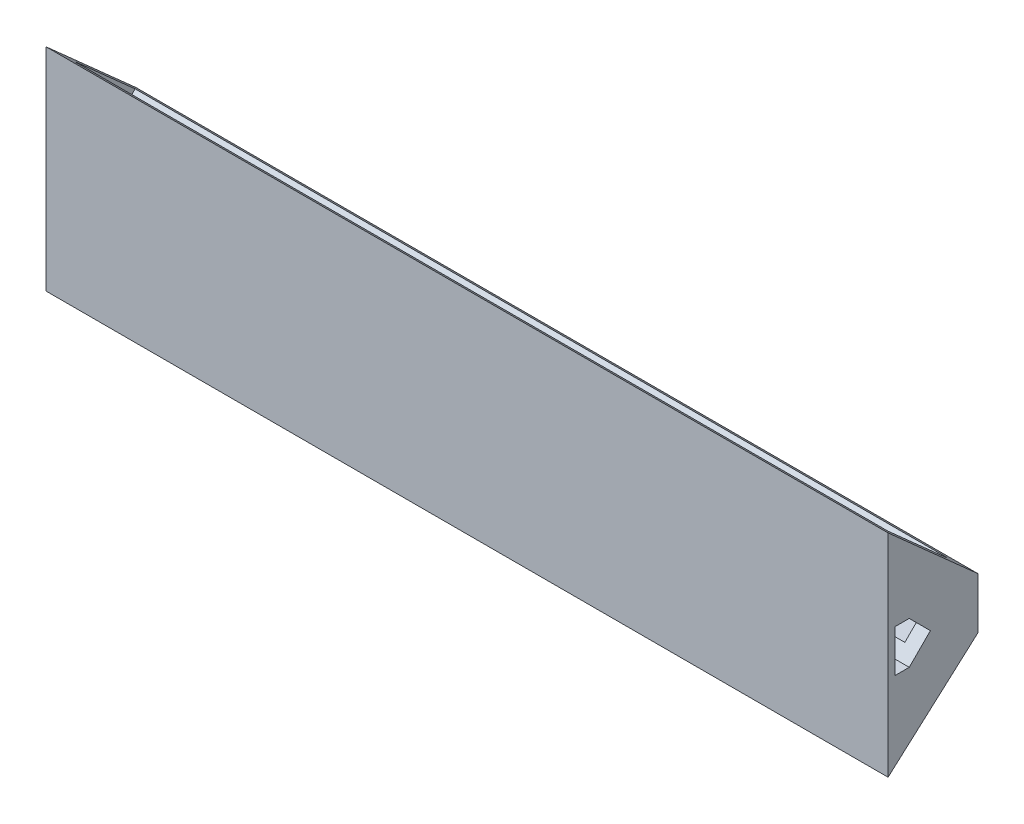
SolidWorks part; units mm, degrees
ref_plane "Front Plane" through (0, 0, 0) normal (0, 0, 1) x (1, 0, 0)
ref_plane "Top Plane" through (0, 0, 0) normal (0, 1, 0) x (1, 0, 0)
ref_plane "Right Plane" through (0, 0, 0) normal (1, 0, 0) x (0, 0, -1)
sketch "Sketch1" plane through (0, 0, 0) normal (0, 0, 1) x (1, 0, 0)
  line L0 (-115.4, 3.25) -> (115.4, -3.25) construction
  line L1 (-115.4, 3.25) -> (115.4, 3.25)
  line L2 (-115.4, 3.25) -> (-115.4, -3.25)
  line L3 (-115.4, -3.25) -> (115.4, -3.25)
  line L4 (115.4, 3.25) -> (115.4, -3.25)
  line L5 (-119.4, 7.25) -> (-119.4, -7.25)
  line L6 (-119.4, -7.25) -> (119.4, -7.25)
  line L7 (119.4, 7.25) -> (119.4, -7.25)
  line L8 (-119.4, 7.25) -> (119.4, 7.25)
  dimension "D1" = 6.5
  dimension "D2" = 230.8
  dimension "D3" = 4
sketch "Sketch4" plane through (0, 0, 0) normal (1, 0, 0) x (0, 0, -1)
  line L0 (-20, 8.7261) -> (-20, -2.0023) construction
  line L1 (0, 7.25) -> (0, -7.25) construction
  line L2 (0, 7.25) -> (-25.5, 30)
  line L3 (-25.5, 30) -> (-25.5, -30)
  line L4 (-25.5, 0) -> (0, 0) construction
  line L5 (-23.5, 6) -> (-23.5, -6)
  line L6 (-23.5, 6) -> (-19.5, 6)
  line L7 (-19.5, 6) -> (-13.5, 0)
  line L8 (-20.5, 4.0321) -> (-20.5, -1.7233) construction
  line L9 (0, -7.25) -> (-25.5, -30)
  line L10 (-19.5, -6) -> (-13.5, 0)
  line L11 (-23.5, -6) -> (-19.5, -6)
  line L12 (0, 7.25) -> (0, -7.25)
  point P22 (-23.5, 0)
  dimension "D1" = 20
  dimension "D2" = 3
  dimension "D3" = 2
  dimension "D4" = 45
  dimension "D5" = 0.5
  dimension "D6" = 6
  dimension "D7" = 4
  dimension "D8" = 30
extrude "Boss-Extrude1" add sketch "Sketch4" along normal up to vertex (119.4 mm away) and the other way up to vertex (119.4 mm away) up to point (119.4, 7.25, 0) other way up to point (-119.4, 7.25, 0)
extrude "Cut-Extrude1" cut sketch "Sketch1" along normal blind 20 contours L1 L4 L3 L2
shell "Shell1" thickness 4 removed face at (0, 18.625, 12.75) removed face at (0, -18.625, 12.75)
chamfer "Chamfer1" distance 4 angle 45 2 edges at (0, -7.25, 4) (0, 7.25, 4)
